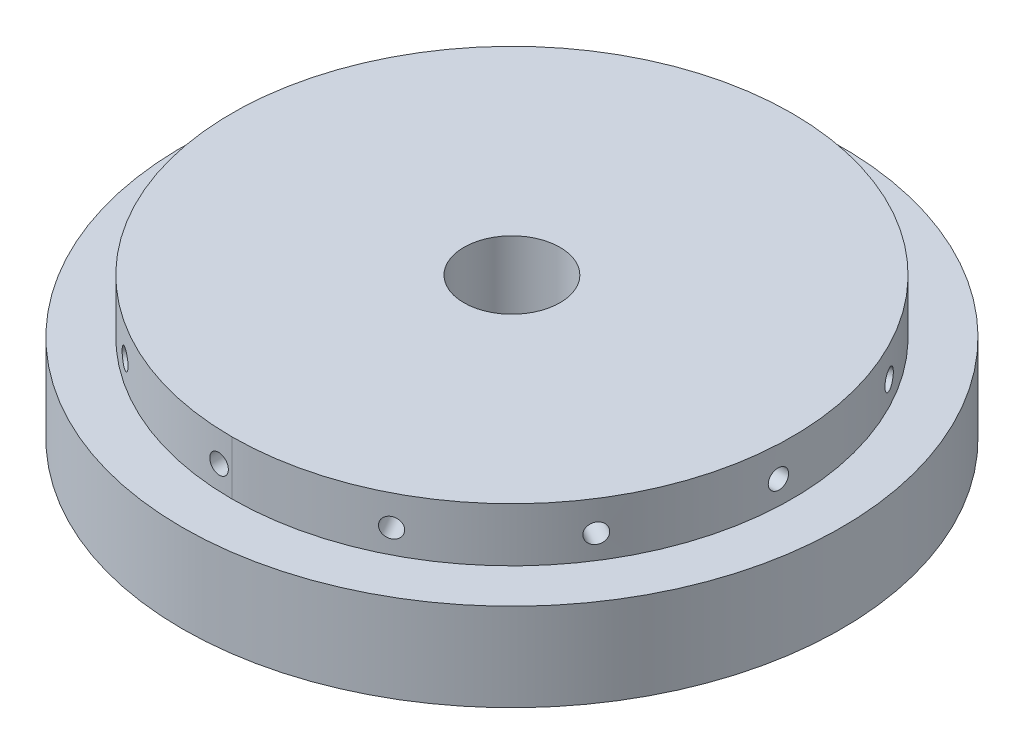
SolidWorks part; units mm, degrees
ref_plane "Front Plane" through (0, 0, 0) normal (0, 0, 1) x (1, 0, 0)
ref_plane "Top Plane" through (0, 0, 0) normal (0, 1, 0) x (1, 0, 0)
ref_plane "Right Plane" through (0, 0, 0) normal (1, 0, 0) x (0, 0, -1)
sketch "Sketch1" plane through (0, 0, 0) normal (0, 1, 0) x (1, 0, 0)
  circle A0 centre (0, 0) radius 64.77
  circle A1 centre (0, 0) radius 76.2
  circle A2 centre (0, 0) radius 56.1975
  circle A4 centre (0, 0) radius 62.865
  dimension "D1" = 152.4
  dimension "D3" = 112.395
  dimension "D2" = 129.54
  dimension "D4" = 13.335
extrude "Boss-Extrude1" add sketch "Sketch1" along normal blind 17.526 contours A0 A2 | A0 A4 region at (-62.938, 0, 0) region at (-61.0869, 0, 0)
extrude "Boss-Extrude2" add sketch "Sketch1<4>" along normal blind 5.08 and the other way blind 15.24 contours A1 A0 | A0 A4 region at (-62.938, 0, 0) region at (-74.0447, 0, 0)
sketch "Sketch1<4>" plane through (0, 0, 0) normal (0, 1, 0) x (1, 0, 0) same geometry as "Sketch1"
sketch "Sketch3" plane through (0, -15.24, 0) normal (0, -1, 0) x (1, 0, 0)
  line L0 (0, 0) -> (-65.7887, 5.7558) construction
  line L1 (0, 0) -> (0, 69.85) construction
  line L2 (0, 0) -> (48.9804, 58.3726)
  line L3 (0, 0) -> (13.232, 75.0424)
  line L4 (-13.335, -54.5925) -> (-13.335, -60.117)
  line L5 (13.335, -54.5925) -> (13.335, -60.117)
  line L6 (-13.335, -60.117) -> (13.335, -60.117)
  line L7 (-13.335, -60.117) -> (-13.335, -61.4344)
  line L8 (-23.7501, -50.9322) -> (-26.5679, -56.975)
  line L9 (0, 0) -> (-23.7501, -50.9322) construction
  line L10 (-65.2934, 11.4174) -> (-61.874, 11.1182)
  line L11 (-66.284, 0.0941) -> (-62.8647, -0.205)
  line L12 (-66.0236, -5.8708) -> (-62.6433, -5.2748)
  line L13 (-64.0498, -17.0646) -> (-60.6695, -16.4686)
  line L14 (-65.0367, -11.4677) -> (0, 0) construction
  line L15 (27.9275, 60.1135) -> (26.7536, 56.8881)
  line L16 (17.2465, 64.0011) -> (16.0725, 60.7757)
  line L17 (38.0961, -54.2427) -> (35.8898, -51.6133)
  line L18 (46.8033, -46.9365) -> (44.597, -44.3071)
  line L19 (-3.0468, 69.7835) -> (0, 0) construction
  line L20 (0, 0) -> (-21.0043, 66.6171) construction
  circle A0 centre (-65.7887, 5.7558) radius 5.6833
  circle A1 centre (-3.0468, 69.7835) radius 1.3589
  circle A2 centre (0, 0) radius 76.2 construction
  circle A5 centre (0, 0) radius 56.1975 construction
  arc A7 (-26.5679, -56.975) -> (-13.335, -61.4344) centre (0, 0) ccw
  arc A9 (-23.7501, -50.9322) -> (-13.335, -54.5925) centre (0, 0) ccw
  circle A10 centre (-65.7887, 5.7558) radius 2.5083
  circle A11 centre (-65.0367, -11.4677) radius 5.6832
  circle A13 centre (-65.0367, -11.4677) radius 2.5082
  circle A14 centre (0, 0) radius 62.865 construction
  circle A15 centre (22.587, 62.0573) radius 5.6832
  circle A16 centre (22.587, 62.0573) radius 2.5082
  circle A17 centre (42.4497, -50.5896) radius 5.6832
  circle A18 centre (42.4497, -50.5896) radius 2.5082
  arc A19 (-62.6433, -5.2748) -> (-60.6695, -16.4686) centre (0, 0) ccw
  circle A20 centre (-21.0043, 66.6171) radius 1.5
  circle A21 centre (0, 0) radius 62.865
  point P0 (0, -60.117)
  point P38 (0, 0)
  point P56 (0, 0)
  circle M49 centre (0, 0) radius 62.865
  dimension "D4" = 11.3665
  dimension "D5" = 2.7178
  dimension "D11" = 5.0165
  dimension "D17" = 3
  dimension "D1" = 66.04
  dimension "D3" = 69.85
  dimension "D6" = 30
  dimension "D7" = 10
  dimension "D9" = 26.67
  dimension "D8" = 5.5245
  dimension "D10" = 25
  dimension "D2" = 82.5
  dimension "D15" = 2.5
  dimension "D16" = 15
  dimension "D12" = 15
  dimension "D14" = 3
extrude "Cut-Extrude1" cut sketch "Sketch3" against normal blind 1.8415 contours A11 A13 M49 | A11 L13 M49 | A13 | A11 L12 M49 | A0 A10 M49 | A10 | A0 L11 M49 | A0 L10 M49 region at (-62.774, -15.24, 10.8743) region at (-63.6243, -15.24, 10.8507) region at (-63.7086, -15.24, 0.1915) region at (-63.4495, -15.24, -5.7433) region at (-64.265, -15.24, -5.9885) region at (-61.5874, -15.24, -16.304) region at (-65.7887, -15.24, 5.7558) region at (-65.0367, -15.24, -11.4677)
extrude "Cut-Extrude2" cut sketch "Sketch3<3>" against normal blind 12.7 contours A1 region at (-3.0468, -15.24, 69.7835)
sketch "Sketch3<3>" plane through (0, -15.24, 0) normal (0, -1, 0) x (1, 0, 0) same geometry as "Sketch3"
sketch "Sketch6" plane through (0, -13.3985, 0) normal (0, -1, 0) x (1, 0, 0)
  line L0 (-65.0367, -11.4677) -> (0, 0) construction
  line L1 (0, 0) -> (-65.7887, 5.7558) construction
  arc A0 (-65.2934, 11.4174) -> (-66.284, 0.0941) centre (-65.7887, 5.7558) ccw construction
  arc A1 (-65.2934, 11.4174) -> (-66.284, 0.0941) centre (-65.7887, 5.7558) ccw
  circle A2 centre (-65.7887, 5.7558) radius 2.5083
  circle A3 centre (-65.0367, -11.4677) radius 2.5082
  point P9 (0, 0)
  dimension "D1" = 5.0165
  dimension "D3" = 15
  dimension "D2" = 2
extrude "Cut-Extrude4" cut sketch "Sketch6" against normal blind 12.5095 contours A3 | A2 region at (-65.0367, -13.3985, -11.4677)
pattern_circular "CirPattern2" count 12 over 360 about axis through (0, -15.24, 0) along (0, 1, 0) of "Cut-Extrude2"
ref_plane "Plane1" through (0, 0, 76.2) normal (0, 0, 1) x (1, 0, 0)
sketch "Sketch5" plane through (0, 0, 76.2) normal (0, 0, 1) x (1, 0, 0)
  line L0 (-3.0468, -15.24) -> (-3.0468, 10.5664) construction
  line L1 (-4.4057, -15.24) -> (-1.6879, -15.24) construction
  line L3 (-76.2, -15.24) -> (76.2, -15.24) construction
  line L4 (76.2, 5.08) -> (-76.2, 5.08) construction
  line L5 (-76.2, -15.24) -> (76.2, -15.24)
  line L6 (76.2, 5.08) -> (-76.2, 5.08)
  circle A0 centre (-3.0468, 10.5664) radius 2.2479
  dimension "D2" = 4.4958
  dimension "D1" = 5.4864
extrude "Cut-Extrude3" cut sketch "Sketch5" against normal up to surface (20.0082 mm away) contours A0 region at (-3.0468, 10.5664, 76.2) up to face at (0, 17.526, 56.1975)
extrude "Boss-Extrude3" add sketch "Sketch3<11>" along normal blind 10.16 from surface contours L4 A9 L8 A7 L7 starting at face at (0, 0, 56.1975)
sketch "Sketch3<11>" plane through (0, -15.24, 0) normal (0, -1, 0) x (1, 0, 0) same geometry as "Sketch3"
pattern_circular "CirPattern3" count 6 over 360 about axis through (0, 17.526, 0) along (0, 1, 0) of "Boss-Extrude3"
fillet "Fillet1" radius 1.5875 12 edges at (-62.6258, -5.08, -5.479) (-59.8713, -5.08, -19.1688) (-26.5679, -5.08, -56.975) (-13.335, -5.08, -61.4344) (36.0579, -5.08, -51.496) (46.5363, -5.08, -42.2657) (62.6258, -5.08, 5.479) (59.8713, -5.08, 19.1688) (26.5679, -5.08, 56.975) (13.335, -5.08, 61.4344) (-36.0579, -5.08, 51.496) (-46.5363, -5.08, 42.2657)
pattern_circular "CirPattern4" count 12 over 360 about axis through (0, 17.526, 0) along (0, 1, 0) of "Cut-Extrude3"
sketch "Sketch8" plane through (0, 17.526, 0) normal (0, 1, 0) x (1, 0, 0)
  arc A0 (-34.7117, -52.4129) -> (12.0518, -61.699) centre (0, 0) ccw construction
  arc A1 (-34.7117, -52.4129) -> (12.0518, -61.699) centre (0, 0) ccw
  circle A2 centre (0, 0) radius 62.865
  circle M2 centre (0, 0) radius 56.1975
extrude "Cut-Extrude5" [suppressed] cut sketch "Sketch8" against normal up to surface (17.526 mm away) contours A1 A2 M2 up to face at (42.8898, 0, 37.3465)
sketch "Sketch9" plane through (0, 0, 0) normal (0, 0, 1) x (1, 0, 0)
  line L0 (0, 5.08) -> (0, 17.526)
  line L1 (76.2, 5.08) -> (-76.2, 5.08) construction
  line L2 (64.77, 17.526) -> (-64.77, 17.526) construction
split line "Split Line2"
extrude "Cut-Extrude7" cut sketch "Sketch3<24>" against normal blind 7.9375 contours A20
sketch "Sketch3<24>" plane through (0, -15.24, 0) normal (0, -1, 0) x (1, 0, 0) same geometry as "Sketch3"
pattern_circular "CirPattern1" count 3 over 360 about axis through (0, -15.24, 0) along (0, 1, 0) of "Cut-Extrude1", "Cut-Extrude4", "Cut-Extrude7"
extrude "Boss-Extrude4" add sketch "Sketch1<8>" along normal up to surface (17.526 mm away) contours A2 region at (0, 0, 0) up to face at (0, 17.526, 56.1975)
sketch "Sketch1<8>" plane through (0, 0, 0) normal (0, 1, 0) x (1, 0, 0) same geometry as "Sketch1"
sketch "Sketch10" plane through (0, -15.24, 0) normal (0, -1, 0) x (1, 0, 0)
  arc A0 (12.0518, 61.699) -> (-34.7117, 52.4129) centre (0, 0) ccw construction
  arc A1 (12.0518, 61.699) -> (-34.7117, 52.4129) centre (0, 0) ccw
  circle A3 centre (0, 0) radius 62.865
sketch "Sketch11" plane through (0, -15.24, 0) normal (0, -1, 0) x (1, 0, 0)
  circle A0 centre (0, 0) radius 62.9592
sketch "Sketch12" plane through (0, 17.526, 0) normal (0, 1, 0) x (1, 0, 0)
  line L1 (-88.9, -88.9) -> (88.9, -88.9)
  line L2 (-88.9, -88.9) -> (-88.9, 88.9)
  line L3 (-88.9, 88.9) -> (88.9, 88.9)
  line L4 (88.9, -88.9) -> (88.9, 88.9)
  line L5 (-88.9, -88.9) -> (88.9, 88.9) construction
  line L6 (-88.9, 88.9) -> (88.9, -88.9) construction
  point P0 (0, 0)
  dimension "D1" = 177.8
  dimension "D2" = 177.8
sketch "Sketch13" plane through (0, 17.526, 0) normal (0, 1, 0) x (1, 0, 0)
  circle A0 centre (0, 0) radius 11.1125
  dimension "D1" = 22.225
extrude "Cut-Extrude8" cut sketch "Sketch13" against normal through all
equation "\"Middle Coupler Inner Daimeter\"= 3.875in"
equation "\"Middle Coupler  Wall Thickness\" = 0.25in"
equation "\"Middle Coupler Bottom Thickness\"= 0.2in"
equation "\"Bearing Rail Offset\"= 0.45in"
equation "\"3-56 UNF Tap\"= 0.089in"
equation "\"3-48 Tap\"= 0.079in"
equation "\"3-56 UNF Clearance\"= 0.104in"
equation "\"3-48 Clearance\" = 0.104in"
equation "\"Ball Bearing Distance\"= 0.03in"
equation "\"TCA Outer Diameter\" = 6in"
equation "\"Interstage Aeroframe Wall Thickness\" = 0.072in"
equation "\"Compression Spring OD\"= 0.42in"
equation "\"10-24 Tap\"= 0.1495in"
equation "\"10-24 Clearance\"= 0.196in"
equation "\"Lower Stage Fuselage Wall Thickness\" = 0.25in"
equation "\"6-32 Tap\" = 0.107in"
equation "\"6-32 Clearance\" = 0.144in"
equation "\"1/4-20 Tap\" = 0.201in"
equation "\"12-24 Tap\" = 0.177in"
equation "\"D1@Sketch1\"=\"TCA Outer Diameter\""
equation "\"D5@Sketch3\"=\"6-32 Tap\""
equation "\"D2@Sketch5\"=\"12-24 Tap\""
equation "\"D8@Sketch3\"=3/16+0.03"
equation "\"D3@Sketch1\"=\"Middle Coupler Inner Daimeter\" + 0.55"
equation "\"D1@Boss-Extrude1\"=0.15 + \"12-24 Major Diameter\"*2.5"
equation "\"12-24 Major Diameter\"= 0.216in"
equation "\"D1@Cut-Extrude1\"=1/16 + 0.01"
equation "\"D11@Sketch3\"=3/16 + 0.01"
equation "\"D1@Sketch6\"=3/16 + 0.01"
equation "\"D1@Sketch5\"=\"12-24 Major Diameter\""
equation "\"D1@Cut-Extrude4\"=0.4425+0.05"
